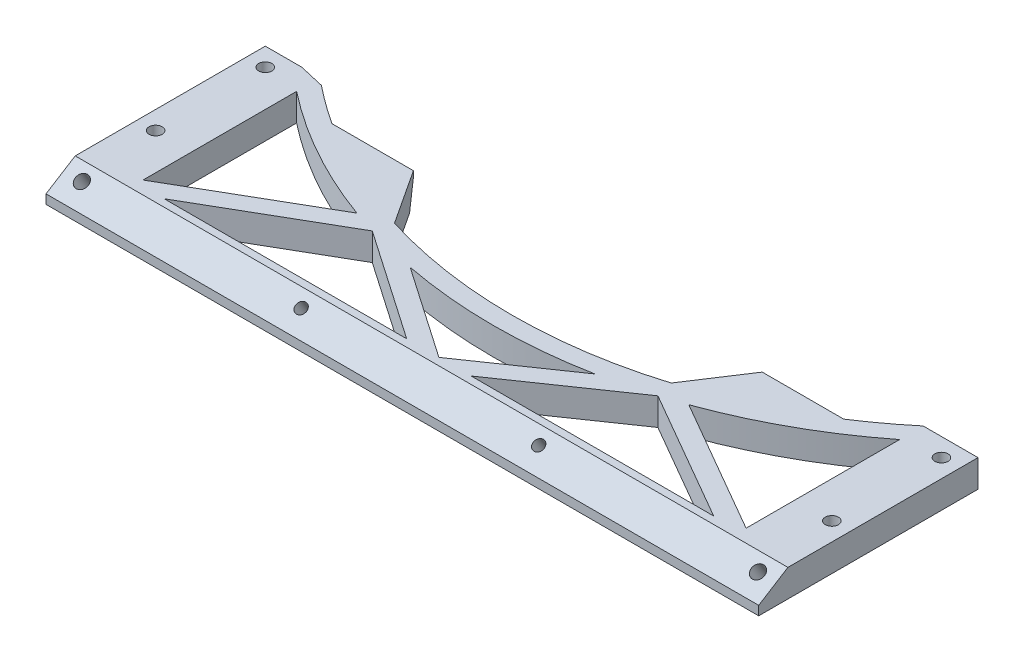
SolidWorks part; units mm, degrees
ref_plane "Front Plane" through (0, 0, 0) normal (0, 0, 1) x (1, 0, 0)
ref_plane "Top Plane" through (0, 0, 0) normal (0, 1, 0) x (1, 0, 0)
ref_plane "Right Plane" through (0, 0, 0) normal (1, 0, 0) x (0, 0, -1)
sketch "Sketch1" plane through (0, 0, 0) normal (0, 1, 0) x (1, 0, 0)
  line L1 (-123.825, 0) -> (123.825, 0)
  line L2 (-123.825, 0) -> (-123.825, 76.2)
  line L4 (123.825, 0) -> (123.825, 76.2)
  line L6 (-123.825, 76.2) -> (-104.775, 76.2)
  line L9 (123.825, 76.2) -> (104.775, 76.2)
  arc A1 (-104.775, 76.2) -> (104.775, 76.2) centre (0, 201.2156) ccw
  point P4 (0, 0)
  point P9 (0, 38.1)
  dimension "D3" = 247.65
  dimension "D4" = 38.1
  dimension "D1" = 19.05
  dimension "D2" = 76.2
  dimension "D6" = 19.05
extrude "Boss-Extrude1" add sketch "Sketch1" along normal blind 9.525
sketch "Sketch2" plane through (0, 9.525, 0) normal (0, 1, 0) x (1, 0, 0)
  line L0 (-104.775, 68.021) -> (-104.775, 14.6647)
  line L1 (-104.775, 14.6647) -> (-57.666, 41.8631)
  line L2 (-95.478, 12.7) -> (-11.1919, 12.7)
  line L3 (-95.478, 12.7) -> (-49.6188, 39.1768)
  line L4 (-123.825, 0) -> (-97.0655, 15.4496) construction
  line L5 (-98.653, 18.1993) -> (-95.478, 12.7) construction
  line L6 (0, 12.7) -> (-32.101, 34.8181)
  line L7 (0, 31.75) -> (0, 12.7)
  line L8 (-49.6188, 39.1768) -> (-11.1919, 12.7)
  line L9 (-123.825, 76.2) -> (-123.825, 0) construction
  line L10 (-123.825, 0) -> (123.825, 0) construction
  arc A0 (-104.775, 76.2) -> (104.775, 76.2) centre (0, 201.2156) ccw construction
  arc A1 (-104.775, 68.021) -> (-57.666, 41.8631) centre (0, 201.2156) ccw
  arc A2 (-32.101, 34.8181) -> (0, 31.75) centre (0, 201.2156) ccw
  point P12 (-97.0655, 15.4496)
  dimension "D5" = 6.35
  dimension "D1" = 6.35
  dimension "D2" = 19.05
  dimension "D3" = 6.35
  dimension "D4" = 12.7
  dimension "D6" = 30
extrude "Cut-Extrude1" cut sketch "Sketch2" against normal through all
mirror "Mirror1" about plane through (0, 0, 0) normal (1, 0, 0) of "Cut-Extrude1"
sketch "Sketch3" plane through (0, 9.525, 0) normal (0, 1, 0) x (1, 0, 0)
  line L1 (-123.825, 76.2) -> (-123.825, 0) construction
  line L2 (-104.775, 76.2) -> (-123.825, 76.2) construction
  line L4 (123.825, 0) -> (123.825, 76.2) construction
  line L5 (123.825, 76.2) -> (104.775, 76.2) construction
  circle A0 centre (117.475, 69.85) radius 2.286
  circle A2 centre (-117.475, 69.85) radius 2.286
  circle A4 centre (117.475, 31.75) radius 2.286
  circle A5 centre (-117.475, 31.75) radius 2.286
  dimension "D1" = 4.572
  dimension "D2" = 6.35
  dimension "D3" = 6.35
  dimension "D4" = 6.35
  dimension "D6" = 6.35
  dimension "D7" = 38.1
extrude "Cut-Extrude2" cut sketch "Sketch3" against normal through all
sketch "Sketch5" plane through (-123.825, 0, 0) normal (-1, 0, 0) x (0, 0, 1)
  line L0 (0, 9.525) -> (-10.1455, 9.525)
  line L1 (-76.2, 9.525) -> (0, 9.525) construction
  line L2 (-10.1455, 9.525) -> (0, 3.175)
  line L3 (0, 9.525) -> (0, 0) construction
  line L4 (0, 3.175) -> (0, 9.525)
  line L8 (15.9106, -6.7833) -> (2.4297, 1.6542) construction
extrude "Cut-Extrude3" cut sketch "Sketch5" against normal through all
sketch "Sketch6" plane through (0, 2.2813, 1.4279) normal (0, 0.8477, 0.5305) x (1, 0, 0)
  circle A2 centre (-117.475, 8.8908) radius 2.286 construction
  circle A3 centre (117.475, 8.8908) radius 2.286 construction
  circle A4 centre (-117.475, 8.8908) radius 2.286
  circle A5 centre (117.475, 8.8908) radius 2.286
  circle A10 centre (-41.275, 8.8908) radius 1.905
  circle A11 centre (41.275, 8.8908) radius 1.905
  circle A12 centre (-41.275, 8.8908) radius 2.286 construction
  circle A13 centre (41.275, 8.8908) radius 2.286 construction
  dimension "D1" = 3.81
extrude "Cut-Extrude4" cut sketch "Sketch6" against normal up to next
sketch "Sketch7" plane through (0, 9.525, 0) normal (0, 1, 0) x (1, 0, 0)
  line L0 (-88.9, 64.4549) -> (-63.5, 64.4549)
  line L1 (-63.5, 64.4549) -> (-63.5, 50.9676)
  line L2 (63.5, 50.9676) -> (63.5, 64.4549)
  line L3 (63.5, 64.4549) -> (88.9, 64.4549)
  arc A0 (-104.775, 76.2) -> (104.775, 76.2) centre (0, 201.2156) ccw construction
  arc A1 (-88.9, 64.4549) -> (-63.5, 50.9676) centre (0, 201.2156) ccw
  arc A2 (88.9, 64.4549) -> (63.5, 50.9676) centre (0, 201.2156) cw
  dimension "D1" = 25.4
  dimension "D2" = 127
chamfer "Chamfer2" [suppressed] distance 3.175 angle 60
chamfer "Chamfer3" [suppressed] distance 12.7 distance2 6.35
fillet "Fillet1" [suppressed] radius 1.5875
extrude "Boss-Extrude2" add sketch "Sketch7" against normal up to surface (9.525 mm away) up to face at (-117.475, 0, -7.7919)
chamfer "Chamfer4" distance 7.62 angle 27.11 2 edges at (-76.2, 0, -64.4549) (76.2, 0, -64.4549) first distance on face at (-76.2, 4.7625, -64.4549) first distance on face at (76.2, 4.7625, -64.4549)
chamfer "Chamfer5" distance 17.145 angle 30 1 edges at (-63.5, 4.7625, -50.9676) first distance on face at (-63.5, 5.334, -58.2798)
sketch "Sketch8" plane through (0, -24.5627, -47.9791) normal (0, -0.4557, -0.8901) x (-1, 0, 0)
  line L0 (67.0317, 36.1549) -> (67.0317, 31.8747) construction
  line L1 (60.6035, 36.1549) -> (88.9, 36.1549) construction
  line L2 (67.0317, 31.8747) -> (67.0317, 27.5944) construction
  line L3 (82.5892, 27.5944) -> (58.0465, 27.5944) construction
  circle A0 centre (79.7317, 31.8747) radius 1.905
  circle A1 centre (67.0317, 31.8747) radius 1.905
  dimension "D1" = 3.81
  dimension "D2" = 12.7
  dimension "D3" = 15.5575
extrude "Cut-Extrude5" cut sketch "Sketch8" against normal blind 7.9375
mirror "Mirror3" about plane through (0, 0, 0) normal (1, 0, 0) of "Cut-Extrude5"
chamfer "Chamfer6" distance 17.145 angle 30 1 edges at (63.5, 4.7625, -50.9676) first distance on face at (63.5, 5.334, -58.2798)
chamfer "Chamfer7" distance 3.175 distance2 6.35 1 edges at (-104.775, 4.7625, -76.2) first distance on face at (-94.0931, 5.32, -68.225)
